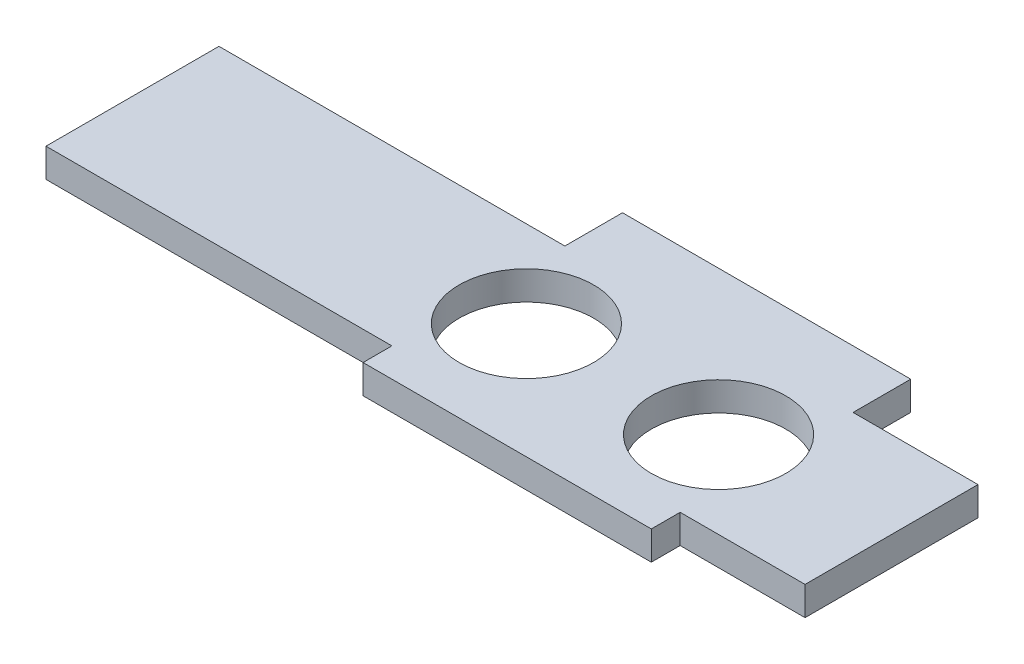
SolidWorks part; units mm, degrees
ref_plane "Front Plane" through (0, 0, 0) normal (0, 0, 1) x (1, 0, 0)
ref_plane "Top Plane" through (0, 0, 0) normal (0, 1, 0) x (1, 0, 0)
ref_plane "Right Plane" through (0, 0, 0) normal (1, 0, 0) x (0, 0, -1)
sketch "Sketch1" plane through (0, 0, 0) normal (0, 1, 0) x (1, 0, 0)
  line L0 (-3, 0) -> (-3, 50000) construction
  line L1 (3, 0) -> (3, 50000) construction
  line L2 (5, 0) -> (5, 50000) construction
  line L3 (-30.5, 9) -> (5.5, 9)
  line L4 (-30.5, 9) -> (-30.5, -9)
  line L5 (-30.5, -9) -> (5.5, -9)
  line L6 (5.5, 9) -> (5.5, -9) construction
  line L7 (-5, 0) -> (-5, 50000) construction
  line L9 (25.5, 9) -> (-10.5, 9)
  line L10 (25.5, 9) -> (25.5, -9)
  line L11 (25.5, -9) -> (-10.5, -9)
  line L12 (-10.5, 9) -> (-10.5, -9) construction
  line L13 (-30.5, 9) -> (25.5, 9)
  line L14 (-30.5, 9) -> (-30.5, -9)
  line L15 (-30.5, -9) -> (25.5, -9)
  line L16 (25.5, 9) -> (25.5, -9)
  circle A0 centre (0, 0) radius 3 construction
  circle A1 centre (-12.5, 0) radius 7
  circle A2 centre (7.5, 0) radius 7
  circle A3 centre (-10, 0) radius 15 construction
  circle A4 centre (10, 0) radius 15 construction
  point P11 (-30.5, 0)
  point P18 (-12.5, 9)
  point P25 (9.3539, 9)
  point P26 (7.5, 9)
  point P28 (25.5, 0)
  dimension "D1" = 6
  dimension "D2" = 36
  dimension "D5" = 14
  dimension "D6" = 14
  dimension "D9" = 2
  dimension "D7" = 2
  dimension "D8" = 7
  dimension "D10" = 12.5
  dimension "D3" = 7
  dimension "D4" = 18
  dimension "D11" = 7.5
  dimension "D12" = 36
extrude "BaseShape" add sketch "Sketch1" along normal blind 3 contours A2 | L14 L13 L16 L15 | A1 region at (7.5, 0, 0)
sketch "Sketch2" plane through (0, 0, 0) normal (0, -1, 0) x (1, 0, 0)
  line L0 (-30.5, -9) -> (25.5, -9) construction
  line L1 (-30.5, -9) -> (-53.5, -9)
  line L2 (-30.5, -9) -> (-30.5, 9)
  line L3 (-30.5, 9) -> (-53.5, 9)
  line L4 (-53.5, -9) -> (-53.5, 9)
  line L5 (-17.5, -9) -> (12.5, -9)
  line L6 (-17.5, -9) -> (-17.5, -15)
  line L7 (-17.5, -15) -> (12.5, -15)
  line L8 (12.5, -9) -> (12.5, -15)
  line L9 (-30.5, -9) -> (-17.5, -9) construction
  line L10 (12.5, -9) -> (25.5, -9) construction
  line L11 (-17.5, 9) -> (-17.5, 12)
  line L12 (-30.5, 9) -> (25.5, 9) construction
  line L13 (-17.5, 12) -> (12.5, 12)
  line L14 (12.5, 12) -> (12.5, 9)
  line L15 (12.5, 9) -> (-17.5, 9)
  dimension "D1" = 23
  dimension "D2" = 6
  dimension "D3" = 30
  dimension "D4" = 3
extrude "FingerJoints" add sketch "Sketch2" against normal up to surface (3 mm away) up to face at (-2.5, 3, 0)
